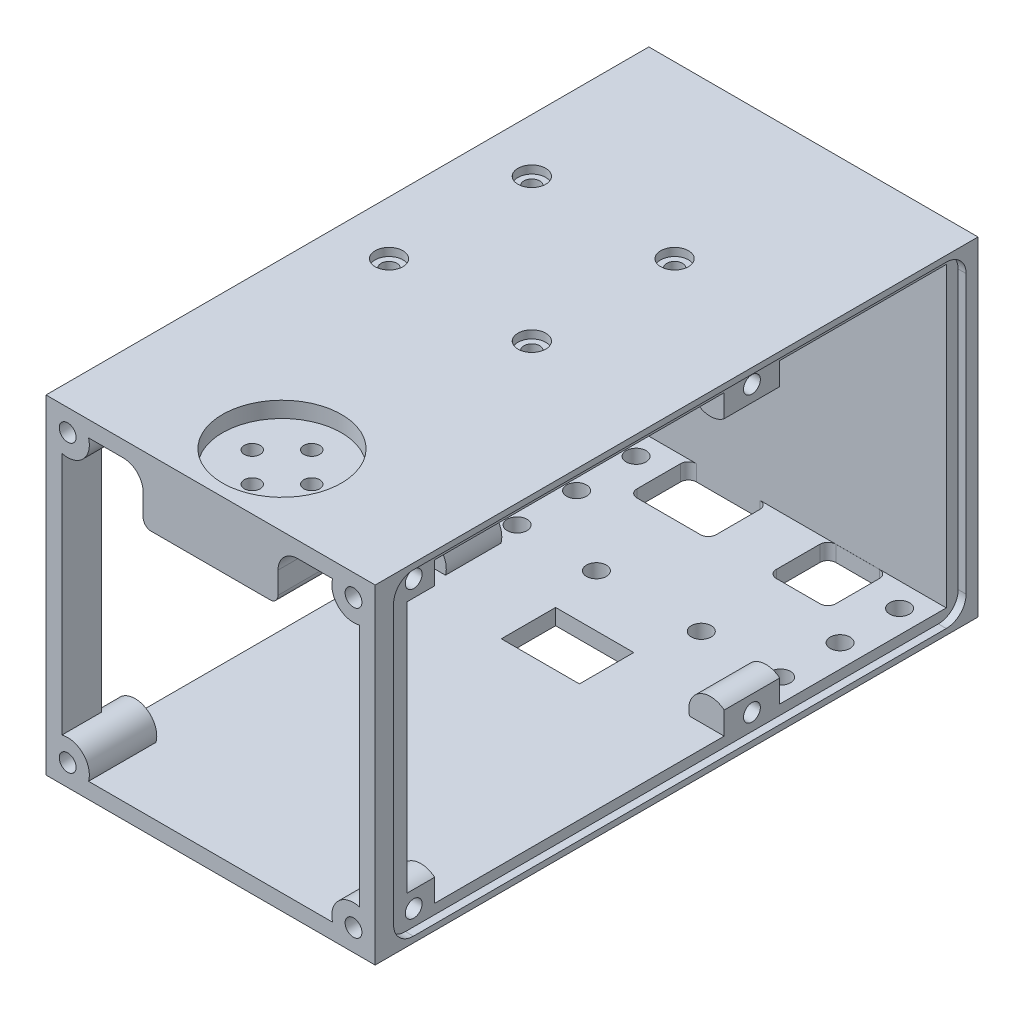
SolidWorks part; units mm, degrees
ref_plane "Front Plane" through (0, 0, 0) normal (1, 0, 0) x (0, 1, 0)
ref_plane "Top Plane" through (0, 0, 0) normal (0, 0, 1) x (0, 1, 0)
ref_plane "Right Plane" through (0, 0, 0) normal (0, 1, 0) x (-1, 0, 0)
sketch "Sketch1" plane through (0, 0, 0) normal (0, 0, 1) x (0, 1, 0)
  line L0 (-41.5, -41.5) -> (41.5, -41.5)
  line L1 (41.5, -41.5) -> (41.5, 41.5)
  line L2 (41.5, 41.5) -> (-41.5, 41.5)
  line L3 (-41.5, 41.5) -> (-41.5, -41.5)
  line L5 (-32.5, -37.5) -> (32.5, -37.5)
  line L6 (-37.5, -32.5) -> (-37.5, 32.5)
  line L7 (-32.5, 37.5) -> (32.5, 37.5)
  line L8 (37.5, -32.5) -> (37.5, 32.5)
  line L9 (37.5, -37.5) -> (-37.5, -37.5)
  line L10 (37.5, -37.5) -> (37.5, 37.5)
  line L11 (37.5, 37.5) -> (-37.5, 37.5)
  line L12 (-37.5, -37.5) -> (-37.5, 37.5)
  line L13 (37.5, -37.5) -> (-37.5, 37.5) construction
  line L14 (37.5, 37.5) -> (-37.5, -37.5) construction
  circle A1 centre (-36.0624, 36.0624) radius 2
  circle A2 centre (-36.0624, -36.0624) radius 2
  circle A3 centre (36.0624, -36.0624) radius 2
  circle A4 centre (36.0624, 36.0624) radius 2
  point P2 (0, 0)
  point P5 (0, 0)
  point P20 (-37.5, 37.5)
  point P23 (-37.5, -37.5)
  point P28 (37.5, 37.5)
  dimension "D1" = 75
  dimension "D2" = 83
  dimension "D3" = 83
  dimension "D4" = 75
  dimension "D7" = 37.5
  dimension "D8" = 37.5
  dimension "D9" = 4
  dimension "D10" = 4
extrude "Boss-Extrude1" add sketch "Sketch1" along normal blind 150 contours L2 L3 L0 L1 A4 L10 L8 A3 L9 L5 A2 L12 L6 A1 L11 L7 | L11 A1 | L12 A1 | L9 A2 | L12 A2 | L10 A3 | L9 A3 | L11 A4 | L10 A4 region at (0, -40.3262, 0) region at (37.7279, -36.0624, 0) region at (37.7279, 36.0624, 0) region at (36.0624, 37.7279, 0) region at (36.0624, -37.7279, 0) region at (-36.0624, 37.7279, 0) region at (-36.0624, -37.7279, 0) region at (-37.7279, 36.0624, 0) region at (-37.7279, -36.0624, 0)
sketch "Sketch2" plane through (0, 0, 0) normal (0, 0, -1) x (1, 0, 0)
  line L4 (-41.5, 41.5) -> (-41.5, -41.5)
  line L5 (-41.5, -41.5) -> (41.5, -41.5)
  line L6 (41.5, -41.5) -> (41.5, 41.5)
  line L7 (41.5, 41.5) -> (-41.5, 41.5)
  line L8 (-41.5, 41.5) -> (-41.5, -41.5)
  line L9 (-41.5, -41.5) -> (41.5, -41.5)
  line L10 (41.5, -41.5) -> (41.5, 41.5)
  line L11 (41.5, 41.5) -> (-41.5, 41.5)
  dimension "D1" = 0
extrude "Boss-Extrude2" add sketch "Sketch2" against normal blind 4
sketch "Sketch3" plane through (0, 0, 150) normal (0, 0, 1) x (1, 0, 0)
  circle A0 centre (-36.0355, 36.0355) radius 5.4645
  circle A2 centre (36.0355, 36.0355) radius 5.4645
  circle A3 centre (36.0355, -36.0355) radius 5.4645
  circle A4 centre (-36.0355, -36.0355) radius 5.4645
  point P14 (0, 0)
  dimension "D1" = 10.9289
  dimension "D2" = 4
extrude "Boss-Extrude3" add sketch "Sketch3" against normal blind 10
sketch "Sketch4" plane through (0, 0, 150) normal (0, 0, 1) x (1, 0, 0)
  circle A0 centre (-36.0355, 36.0355) radius 2.125
  circle A1 centre (36.0355, 36.0355) radius 2.125
  circle A2 centre (36.0355, -36.0356) radius 2.125
  circle A3 centre (-36.0356, -36.0355) radius 2.125
  point P12 (0, 0)
  dimension "D1" = 4
extrude "Cut-Extrude1" cut sketch "Sketch4" against normal blind 4
sketch "Sketch6" plane through (-41.5, 0, 0) normal (-1, 0, 0) x (0, -1, 0)
  line L0 (-41.5, 0) -> (41.5, 0) construction
  line L1 (37.5, 4) -> (-37.5, 4)
  line L2 (37.5, 4) -> (37.5, 136.5853)
  line L3 (34.0853, 140) -> (-34.0853, 140)
  line L4 (-37.5, 4) -> (-37.5, 136.5853)
  line L7 (-41.5, 150) -> (41.5, 150) construction
  line L8 (-41.5, 150) -> (-41.5, 0) construction
  line L9 (41.5, 150) -> (41.5, 0) construction
  arc A2 (37.5, 136.5853) -> (34.0853, 140) centre (34.0853, 136.5853) ccw
  arc A3 (-34.0853, 140) -> (-37.5, 136.5853) centre (-34.0853, 136.5853) ccw
  point P0 (0, 59.5)
  point P1 (34.5, 6)
  point P2 (34.5, 7.2991)
  point P3 (-34.5, 6)
  point P4 (-34.5, 7.1234)
  point P14 (-34.5, 136.5853)
  dimension "D1" = 4
  dimension "D2" = 10
  dimension "D3" = 4
  dimension "D4" = 4
extrude "Cut-Extrude3" cut sketch "Sketch6" against normal through all
sketch "Sketch9" plane through (0, 0, 150) normal (0, 0, 1) x (1, 0, 0)
  line L0 (-41.5, 37.5) -> (41.5, 37.5) construction
  line L1 (15, 25) -> (-15, 25)
  line L2 (17, 27) -> (17, 32.5)
  line L4 (-17, 27) -> (-17, 32.5)
  line L9 (-22, 37.5) -> (22, 37.5)
  arc A0 (-17, 32.5) -> (-22, 37.5) centre (-22, 32.5) ccw
  arc A1 (17, 32.5) -> (22, 37.5) centre (22, 32.5) cw
  arc A2 (-15, 25) -> (-17, 27) centre (-15, 27) cw
  arc A3 (15, 25) -> (17, 27) centre (15, 27) ccw
  point P8 (-17, 25)
  point P15 (17, 25)
  dimension "D2" = 5
  dimension "D4" = 5
  dimension "D5" = 2
  dimension "D1" = 25
  dimension "D3" = 5
  dimension "D6" = 5
  dimension "D7" = 30
extrude "Boss-Extrude4" add sketch "Sketch9" against normal blind 40
sketch "Sketch10" plane through (0, -41.5, 0) normal (0, -1, 0) x (1, 0, 0)
  line L0 (-41.5, 150) -> (-41.5, 0) construction
  line L1 (-23.5, 4) -> (-7.5, 4)
  line L2 (-25.5, 6) -> (-25.5, 17)
  line L3 (-23.5, 19) -> (-7.5, 19)
  line L4 (-5.5, 6) -> (-5.5, 17)
  line L6 (-41.5, 0) -> (41.5, 0) construction
  line L7 (9.6618, 6.0152) -> (9.6618, 17.0152)
  line L8 (24.6618, 6.0152) -> (24.6618, 17.0152)
  line L9 (11.6618, 4.0152) -> (22.6618, 4.0152)
  line L10 (11.6618, 19.0152) -> (22.6618, 19.0152)
  line L11 (-9.85, 53.15) -> (9.85, 53.15)
  line L12 (-9.85, 53.15) -> (-9.85, 66.85)
  line L13 (-9.85, 66.85) -> (9.85, 66.85)
  line L14 (9.85, 53.15) -> (9.85, 66.85)
  line L15 (-9.85, 53.15) -> (9.85, 66.85) construction
  line L16 (-9.85, 66.85) -> (9.85, 53.15) construction
  arc A0 (-7.5, 19) -> (-5.5, 17) centre (-7.5, 17) cw
  arc A1 (-7.5, 4) -> (-5.5, 6) centre (-7.5, 6) ccw
  arc A2 (-23.5, 4) -> (-25.5, 6) centre (-23.5, 6) cw
  arc A3 (-25.5, 17) -> (-23.5, 19) centre (-23.5, 17) cw
  arc A4 (9.6618, 17.0152) -> (11.6618, 19.0152) centre (11.6618, 17.0152) cw
  arc A5 (11.6618, 4.0152) -> (9.6618, 6.0152) centre (11.6618, 6.0152) cw
  arc A8 (22.6618, 4.0152) -> (24.6618, 6.0152) centre (22.6618, 6.0152) ccw
  arc A9 (24.6618, 17.0152) -> (22.6618, 19.0152) centre (22.6618, 17.0152) ccw
  circle A10 centre (33.7227, 40) radius 2.5
  circle A11 centre (33.7227, 25) radius 2.5
  circle A12 centre (33.7227, 10) radius 2.5
  circle A13 centre (-32.7185, 40) radius 2.5
  circle A14 centre (-32.7185, 10) radius 2.5
  circle A15 centre (-32.7185, 25) radius 2.5
  circle A16 centre (-12.7185, 40) radius 2.5
  circle A17 centre (13.7227, 40) radius 2.5
  point P10 (-5.5, 19)
  point P13 (-5.5, 4)
  point P18 (-25.5, 19)
  point P47 (0, 60)
  point P52 (0, 0)
  point P53 (0, 0)
  dimension "D5" = 2
  dimension "D6" = 2
  dimension "D8" = 5
  dimension "D11" = 5
  dimension "D12" = 20
  dimension "D14" = 19.7
  dimension "D1" = 16
  dimension "D2" = 20
  dimension "D3" = 4
  dimension "D4" = 15
  dimension "D7" = 15
  dimension "D10" = 40
  dimension "D13" = 20
  dimension "D15" = 13.7
  dimension "D16" = 60
  dimension "D9" = 3
extrude "Cut-Extrude4" cut sketch "Sketch10" against normal blind 24
sketch "Sketch11" plane through (0, 41.5, 0) normal (0, 1, 0) x (-1, 0, 0)
  circle A0 centre (-8, 76.9997) radius 2
  circle A1 centre (28, 76.9997) radius 2
  circle A4 centre (-8, 76.9997) radius 3.5
  circle A5 centre (28, 76.9997) radius 3.5
  circle A8 centre (-8, 40.9997) radius 3.5 [skipped]
  circle A9 centre (28, 40.9997) radius 3.5 [skipped]
  circle A10 centre (-8, 40.9997) radius 3.5
  circle A11 centre (-8, 40.9997) radius 2
  circle A12 centre (28, 40.9997) radius 3.5
  circle A13 centre (28, 40.9997) radius 2
  dimension "D13" = 4
  dimension "D14" = 2
  dimension "D4" = 4
  dimension "D3" = 2
  dimension "D2" = 36
  dimension "D15" = 2
extrude "Cut-Extrude5" cut sketch "Sketch11" against normal blind 24 contours A0 | A11 | A13 | A1
extrude "Cut-Extrude6" cut sketch "Sketch11<3>" against normal blind 2
sketch "Sketch11<3>" plane through (0, 41.5, 0) normal (0, 1, 0) x (-1, 0, 0) same geometry as "Sketch11"
sketch "Sketch12" plane through (0, 25, 0) normal (0, -1, 0) x (1, 0, 0)
  line L4 (-15, 150) -> (15, 150) construction
  circle A1 centre (0, 139.5) radius 2
  circle A2 centre (-7.5, 132) radius 2
  circle A3 centre (0, 124.5) radius 2
  circle A4 centre (7.5, 132) radius 2
  dimension "D4" = 4
  dimension "D5" = 4
  dimension "D7" = 4
  dimension "D8" = 4
  dimension "D1" = 15
  dimension "D2" = 7.5
  dimension "D3" = 7.5
  dimension "D6" = 10.5
extrude "Cut-Extrude7" cut sketch "Sketch12" against normal through all
sketch "Sketch13" plane through (0, 41.5, 0) normal (0, 1, 0) x (-1, 0, 0)
  circle A0 centre (0, 132) radius 15
  dimension "D1" = 30
extrude "Cut-Extrude8" cut sketch "Sketch13" against normal blind 4
sketch "Sketch15" plane through (0, 0, 0) normal (0, 0, -1) x (1, 0, 0)
  line L4 (-41.5, 41.5) -> (-41.5, -41.5)
  line L5 (-41.5, -41.5) -> (41.5, -41.5)
  line L6 (41.5, -41.5) -> (41.5, 41.5)
  line L7 (41.5, 41.5) -> (-41.5, 41.5)
  line L8 (-41.5, 41.5) -> (-41.5, -41.5)
  line L9 (-41.5, -41.5) -> (41.5, -41.5)
  line L10 (41.5, -41.5) -> (41.5, 41.5)
  line L11 (41.5, 41.5) -> (-41.5, 41.5)
  dimension "D1" = 0
extrude "Boss-Extrude5" add sketch "Sketch15" along normal blind 2
sketch "Sketch14" plane through (-41.5, 0, 0) normal (-1, 0, 0) x (0, -1, 0)
  line L2 (41.5, -2) -> (-41.5, -2) construction
  line L12 (-35, 1) -> (35, 1)
  line L14 (40, 6) -> (40, 140.3637)
  line L15 (35, 145.3637) -> (-35, 145.3637)
  line L16 (-40, 6) -> (-40, 140.3637)
  arc A4 (-35, 145.3637) -> (-40, 140.3637) centre (-35, 140.3637) ccw
  arc A5 (40, 140.3637) -> (35, 145.3637) centre (35, 140.3637) ccw
  arc A6 (-35, 1) -> (-40, 6) centre (-35, 6) cw
  arc A7 (40, 6) -> (35, 1) centre (35, 6) cw
  point P12 (0, 70.2926)
  dimension "D2" = 3
  dimension "D1" = 5
  dimension "D3" = 5
  dimension "D4" = 70
  dimension "D5" = 40
extrude "Cut-Extrude9" cut sketch "Sketch14" against normal blind 2
mirror "Mirror1" about plane through (0, 0, 0) normal (1, 0, 0) of "Cut-Extrude9"
sketch "Sketch16" plane through (0, 0, 140) normal (0, 0, -1) x (1, 0, 0)
  line L0 (37.5, -37.5) -> (30.771, -37.5) construction
  line L1 (39.5, -37.5) -> (30.771, -37.5)
  line L2 (39.5, -31.8097) -> (39.5, -37.5)
  line L9 (39.5, 35) -> (39.5, -35) construction
  line L12 (-39.5, 37.5) -> (-30.771, 37.5)
  line L13 (-39.5, 31.8097) -> (-39.5, 37.5)
  line L16 (-37.5, -39.5) -> (-37.5, -30.771) [skipped]
  line L17 (-31.8097, -39.5) -> (-37.5, -39.5) [skipped]
  line L18 (37.5, 39.5) -> (37.5, 30.771) [skipped]
  line L19 (31.8097, 39.5) -> (37.5, 39.5) [skipped]
  line L20 (0, 17.8612) -> (0, -10.3279) construction
  line L21 (-39.5, -31.8097) -> (-39.5, -37.5)
  line L22 (-39.5, -37.5) -> (-30.771, -37.5)
  line L23 (39.5, 31.8097) -> (39.5, 37.5)
  line L24 (39.5, 37.5) -> (30.771, 37.5)
  arc A0 (37.5, -30.771) -> (30.771, -37.5) centre (36.0355, -36.0355) ccw construction
  arc A1 (39.5, -31.8097) -> (30.771, -37.5) centre (36.0355, -36.0355) ccw
  arc A6 (-39.5, 31.8097) -> (-30.771, 37.5) centre (-36.0355, 36.0355) ccw
  arc A8 (-31.8097, -39.5) -> (-37.5, -30.771) centre (-36.0355, -36.0355) ccw [skipped]
  arc A9 (31.8097, 39.5) -> (37.5, 30.771) centre (36.0355, 36.0355) ccw [skipped]
  arc A10 (-39.5, -31.8097) -> (-30.771, -37.5) centre (-36.0355, -36.0355) cw
  arc A11 (39.5, 31.8097) -> (30.771, 37.5) centre (36.0355, 36.0355) cw
  point P19 (0, 0)
  point P24 (0, 0)
  dimension "D1" = 4
extrude "Boss-Extrude6" add sketch "Sketch16" along normal blind 7
sketch "Sketch17" plane through (39.5, 0, 0) normal (1, 0, 0) x (0, 1, 0)
  line L1 (40, 140.3637) -> (40, 6) construction
  line L2 (-40, 6) -> (-40, 140.3637) construction
  circle A0 centre (36, 138.2853) radius 2.125
  circle A2 centre (-36, 138.2853) radius 2.125
  dimension "D1" = 4
  dimension "D2" = 4
  dimension "D3" = 72
extrude "Cut-Extrude10" cut sketch "Sketch17" against normal blind 4
mirror "Mirror2" about plane through (0, 0, 0) normal (1, 0, 0) of "Cut-Extrude10"
ref_plane "Plane1" through (0, 0, 60) normal (0, 0, 1) x (1, 0, 0)
sketch "Sketch18" plane through (0, 0, 60) normal (0, 0, 1) x (1, 0, 0)
  line L0 (39.5, -37.5) -> (30.771, -37.5)
  line L1 (39.5, -31.8097) -> (39.5, -37.5)
  line L2 (-39.5, 37.5) -> (-30.771, 37.5)
  line L3 (-39.5, 31.8097) -> (-39.5, 37.5)
  line L4 (0, 17.8612) -> (0, -10.3279) construction
  line L5 (-39.5, -31.8097) -> (-39.5, -37.5)
  line L6 (-39.5, -37.5) -> (-30.771, -37.5)
  line L7 (39.5, 31.8097) -> (39.5, 37.5)
  line L8 (39.5, 37.5) -> (30.771, 37.5)
  arc A0 (39.5, -31.8097) -> (30.771, -37.5) centre (36.0355, -36.0355) ccw
  arc A1 (-39.5, 31.8097) -> (-30.771, 37.5) centre (-36.0355, 36.0355) ccw
  arc A2 (-39.5, -31.8097) -> (-30.771, -37.5) centre (-36.0355, -36.0355) cw
  arc A3 (39.5, 31.8097) -> (30.771, 37.5) centre (36.0355, 36.0355) cw
  point P16 (0, 0)
  point P19 (0, 0)
extrude "Boss-Extrude7" add sketch "Sketch18" against normal blind 14 contours A2 L5 L6 | L7 L8 A3 | L2 A1 L3 | L0 A0 L1 region at (-35.3373, -34.3742, 60)
sketch "Sketch19" plane through (-39.5, 0, 0) normal (-1, 0, 0) x (0, -1, 0)
  line L0 (31.8097, 46) -> (31.8097, 60) construction
  line L1 (45.65, 60) -> (-45.65, 60) construction
  circle A0 centre (35.8097, 53) radius 2.125
  dimension "D1" = 4
  dimension "D2" = 4.25
  dimension "D3" = 7
extrude "Cut-Extrude11" cut sketch "Sketch19" against normal blind 4
sketch "Sketch20" plane through (39.5, 0, 0) normal (1, 0, 0) x (0, 1, 0)
  line L0 (31.8097, 46) -> (31.8097, 60) construction
  line L1 (45.65, 60) -> (-45.65, 60) construction
  circle A0 centre (35.8097, 53) radius 2.125
  dimension "D1" = 4
  dimension "D2" = 7
  dimension "D3" = 4.25
extrude "Cut-Extrude12" cut sketch "Sketch20" against normal blind 4
mirror "Mirror3" about plane through (0, 0, 0) normal (1, 0, 0) of "Cut-Extrude11"
mirror "Mirror4" about plane through (0, 0, 0) normal (1, 0, 0) of "Cut-Extrude12"
sketch "Sketch21" plane through (39.5, 0, 0) normal (1, 0, 0) x (0, 1, 0)
  line L4 (40, 6) -> (40, 140.3637)
  line L5 (35, 145.3637) -> (-35, 145.3637)
  line L6 (-40, 140.3637) -> (-40, 6)
  line L7 (-35, 1) -> (35, 1)
  line L8 (40, 6) -> (40, 140.3637)
  line L9 (35, 145.3637) -> (-35, 145.3637)
  line L10 (-40, 140.3637) -> (-40, 6)
  line L11 (-35, 1) -> (35, 1)
  circle A0 centre (-35.8097, 53) radius 2.125 construction
  circle A1 centre (35.8097, 53) radius 2.125 construction
  circle A2 centre (36, 138.2853) radius 2.125 construction
  circle A3 centre (-36, 138.2853) radius 2.125 construction
  arc A4 (35, 1) -> (40, 6) centre (35, 6) ccw
  arc A5 (40, 140.3637) -> (35, 145.3637) centre (35, 140.3637) ccw
  arc A6 (-35, 145.3637) -> (-40, 140.3637) centre (-35, 140.3637) ccw
  arc A7 (-40, 6) -> (-35, 1) centre (-35, 6) ccw
  arc A8 (35, 1) -> (40, 6) centre (35, 6) ccw
  arc A9 (40, 140.3637) -> (35, 145.3637) centre (35, 140.3637) ccw
  arc A10 (-35, 145.3637) -> (-40, 140.3637) centre (-35, 140.3637) ccw
  arc A11 (-40, 6) -> (-35, 1) centre (-35, 6) ccw
  circle A12 centre (-35.8097, 53) radius 2.125
  circle A13 centre (35.8097, 53) radius 2.125
  circle A14 centre (36, 138.2853) radius 2.125
  circle A15 centre (-36, 138.2853) radius 2.125
  dimension "D1" = 0
sketch "Sketch22" plane through (39.5, 0, 0) normal (1, 0, 0) x (0, 1, 0)
  line L4 (40, 6) -> (40, 140.3637)
  line L5 (35, 145.3637) -> (-35, 145.3637)
  line L6 (-40, 140.3637) -> (-40, 6)
  line L7 (-35, 1) -> (35, 1)
  line L8 (40, 6) -> (40, 140.3637)
  line L9 (35, 145.3637) -> (-35, 145.3637)
  line L10 (-40, 140.3637) -> (-40, 6)
  line L11 (-35, 1) -> (35, 1)
  circle A0 centre (-35.8097, 53) radius 2.125 construction
  circle A1 centre (35.8097, 53) radius 2.125 construction
  circle A2 centre (36, 138.2853) radius 2.125 construction
  circle A3 centre (-36, 138.2853) radius 2.125 construction
  arc A4 (35, 1) -> (40, 6) centre (35, 6) ccw
  arc A5 (40, 140.3637) -> (35, 145.3637) centre (35, 140.3637) ccw
  arc A6 (-35, 145.3637) -> (-40, 140.3637) centre (-35, 140.3637) ccw
  arc A7 (-40, 6) -> (-35, 1) centre (-35, 6) ccw
  arc A8 (35, 1) -> (40, 6) centre (35, 6) ccw
  arc A9 (40, 140.3637) -> (35, 145.3637) centre (35, 140.3637) ccw
  arc A10 (-35, 145.3637) -> (-40, 140.3637) centre (-35, 140.3637) ccw
  arc A11 (-40, 6) -> (-35, 1) centre (-35, 6) ccw
  circle A12 centre (-35.8097, 53) radius 2.125
  circle A13 centre (35.8097, 53) radius 2.125
  circle A14 centre (36, 138.2853) radius 2.125
  circle A15 centre (-36, 138.2853) radius 2.125
  dimension "D1" = 0
